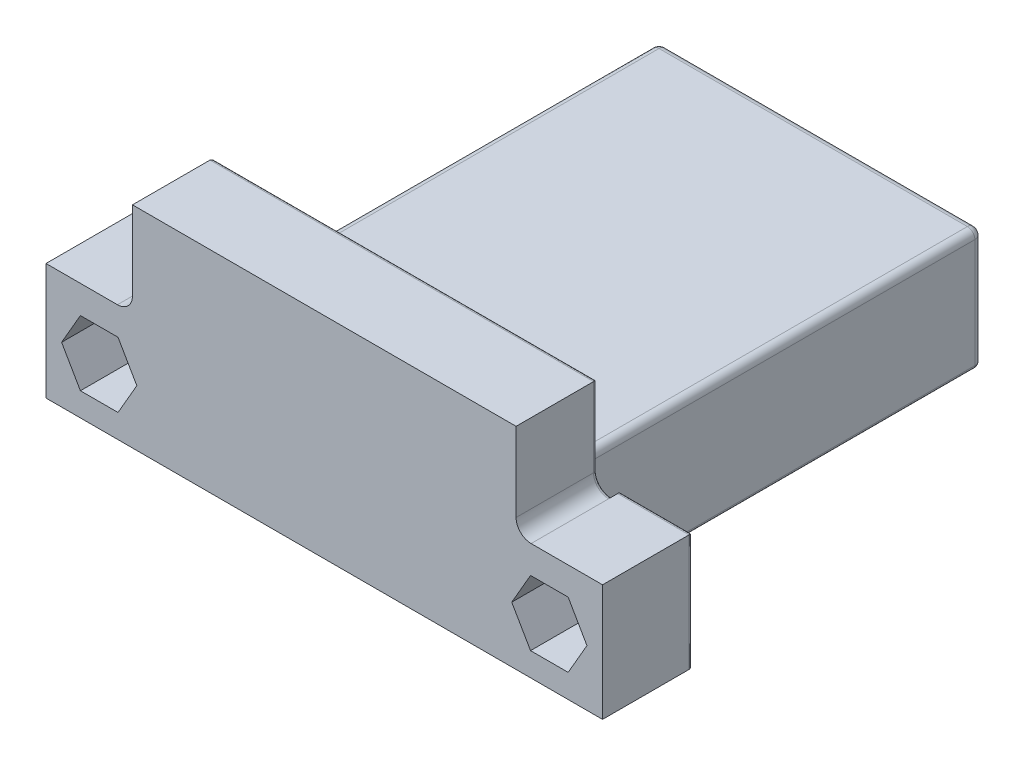
SolidWorks part; units mm, degrees
material "Alliage 1060"
ref_plane "Plan de dessus" through (0, 0, 0) normal (0, 0, 1) x (1, 0, 0)
ref_plane "Plan de droite" through (0, 0, 0) normal (0, 1, 0) x (1, 0, 0)
ref_plane "Plan de face" through (0, 0, 0) normal (1, 0, 0) x (0, 0, -1)
sketch "Esquisse1" plane through (0, 0, 0) normal (0, 1, 0) x (1, 0, 0)
  line L1 (0, 0) -> (-12.5, 0)
  line L2 (0, 0) -> (0, -23)
  line L3 (0, -23) -> (-12.5, -23)
  line L4 (-12.5, 0) -> (-12.5, -23)
  line L9 (-17, -27.5) -> (-17, -28.5)
  line L11 (-17, -28.5) -> (4.5, -28.5)
  line L12 (4.5, -28.5) -> (4.5, -27.5)
  line L14 (-4.2162, 4.5) -> (4.5, 4.5)
  line L16 (4.5, 4.5) -> (-17, 4.5)
  line L17 (4.5, 4.5) -> (4.5, -27.5)
  line L19 (-17, 4.5) -> (-17, -27.5)
  dimension "D1" = 4.5
  dimension "D2" = 4.2162
  dimension "D3" = 12.5
  dimension "D4" = 17
  dimension "D5" = 4.5
  dimension "D6" = 23
  dimension "D7" = 27.5
  dimension "D8" = 28.5
extrude "Boss.-Extru.1" add sketch "Esquisse1" along normal blind 4
sketch "Esquisse10" plane through (0, 0, 28.5) normal (0, 0, 1) x (1, 0, 0)
  line L0 (4.4986, 3.875) -> (4.4986, 0)
  line L1 (4.4986, 0) -> (12.2486, 0)
  line L2 (12.2486, 0) -> (12.2486, 7.75)
  line L3 (12.2486, 7.75) -> (7.4986, 7.75)
  line L4 (7.4986, 7.75) -> (4.4986, 3.875)
extrude "Boss.-Extru.4" add sketch "Esquisse10" against normal blind 6
sketch "Esquisse5" plane through (0, 0, 28.5) normal (0, 0, 1) x (1, 0, 0)
  line L0 (-6.25, 3.875) -> (-6.25, 21.5906) construction
  line L3 (-6.25, 7.75) -> (-6.25, 3.875)
  line L4 (-6.25, 3.875) -> (4.5, 3.875)
  line L8 (4.5, 4) -> (4.5, 3.8768) construction
  line L9 (-17, 0) -> (12.2486, 0) construction
  line L10 (7.5, 7.75) -> (4.5, 3.875)
  line L11 (6.5, 8.75) -> (6.5, 14)
  line L12 (6.5, 14) -> (-6.25, 14)
  line L13 (-6.25, 14) -> (-6.25, 7.75)
  arc A0 (7.5, 7.75) -> (6.5, 8.75) centre (7.5, 8.75) cw
  dimension "D3" = 1
  dimension "D2" = 10.75
  dimension "D4" = 2
extrude "Boss.-Extru.2" add sketch "Esquisse5" against normal blind 5.4
sketch "Esquisse6" plane through (8.4, 0, 22.5) normal (0, 0, 1) x (1, 0, 0)
  line L1 (2.8115, 3.7311) -> (1.5615, 5.8962)
  line L2 (1.5615, 5.8962) -> (-0.9385, 5.8962)
  line L9 (-0.9385, 5.8962) -> (-2.1885, 3.7311)
  line L10 (-2.1885, 3.7311) -> (-0.9385, 1.5661)
  line L11 (-0.9385, 1.5661) -> (1.5615, 1.5661)
  line L12 (1.5615, 1.5661) -> (2.8115, 3.7311)
  circle A1 centre (0.3115, 3.7311) radius 2.5 construction
  circle A2 centre (0.3115, 3.7311) radius 2.1651 construction
  dimension "D1" = 5
extrude "Enlèv. mat.-Extru.1" cut sketch "Esquisse6" along normal up to next
mirror "Symétrie1" about plane through (-6.25, 7.75, 23.1) normal (-1, 0, 0) of "Boss.-Extru.2"
sketch "Esquisse9" plane through (0, 4, 0) normal (0, 1, 0) x (1, 0, 0)
  line L1 (-17, 4.5) -> (4.5, 4.5)
  line L2 (-17, 4.5) -> (-17, -25.5)
  line L3 (-17, -25.5) -> (4.5, -25.5)
  line L4 (4.5, 4.5) -> (4.5, -25.5)
  dimension "D1" = 30
  dimension "D2" = 21.5
  dimension "D3" = 17
  dimension "D4" = 4.5
extrude "Boss.-Extru.3" add sketch "Esquisse9" along normal blind 4
fillet "Congé5" radius 0.5 5 edges at (-17, 4, -4.5) (4.5, 4, -4.5) (4.5, 8, 9.3) (-6.25, 8, -4.5) (-17, 8, 9.3)
fillet "Congé6" radius 0.5 5 edges at (-16.8536, 7.8536, 23.1) (4.3536, 7.8536, 23.1) (-17, 5.6875, 23.1) (4.5, 5.6884, 23.1) (-6.25, 8, 23.1)
ref_plane "Plan1" through (-6.25, 0, 0) normal (1, 0, 0) x (0, 0, -1)
mirror "Symétrie2" about plane through (-6.25, 0, 0) normal (1, 0, 0) of "Boss.-Extru.4"
mirror "Symétrie3" about plane through (-6.25, 0, 0) normal (1, 0, 0) of "Enlèv. mat.-Extru.1"
fillet "Congé8" radius 0.25 17 edges at (-17, 0, 9.25) (-16.8536, 0, -4.3536) (-6.25, 0, -4.5) (4.3536, 0, -4.3536) (4.5, 0, 9.25) (-19.2924, 8.0434, 23.1) (6.7924, 8.0434, 23.1) (-19, 11.375, 23.1) (-24.7486, 3.875, 22.5) (-20.8743, 0, 22.5) (-22.3736, 7.75, 22.5) (4.5, 1.9384, 22.5) (8.3743, 0, 22.5) (12.2486, 3.875, 22.5) (9.8736, 7.75, 22.5) (-6.25, 14, 23.1) (6.5, 11.375, 23.1)
sketch "Esquisse11" plane through (0, 0, 0) normal (0, -1, 0) x (1, 0, 0)
  line L0 (-2.25, 20) -> (-2.25, 26)
  line L4 (-2.25, 26) -> (-10.25, 26)
  line L5 (-10.25, 26) -> (-10.25, 20)
  line L7 (-2.25, 20) -> (-10.25, 20)
  dimension "D1" = 6.5
  dimension "D2" = 3.25
  dimension "D3" = 6
  dimension "D4" = 8
extrude "Enlèv. mat.-Extru.2" cut sketch "Esquisse11" against normal blind 11.5
